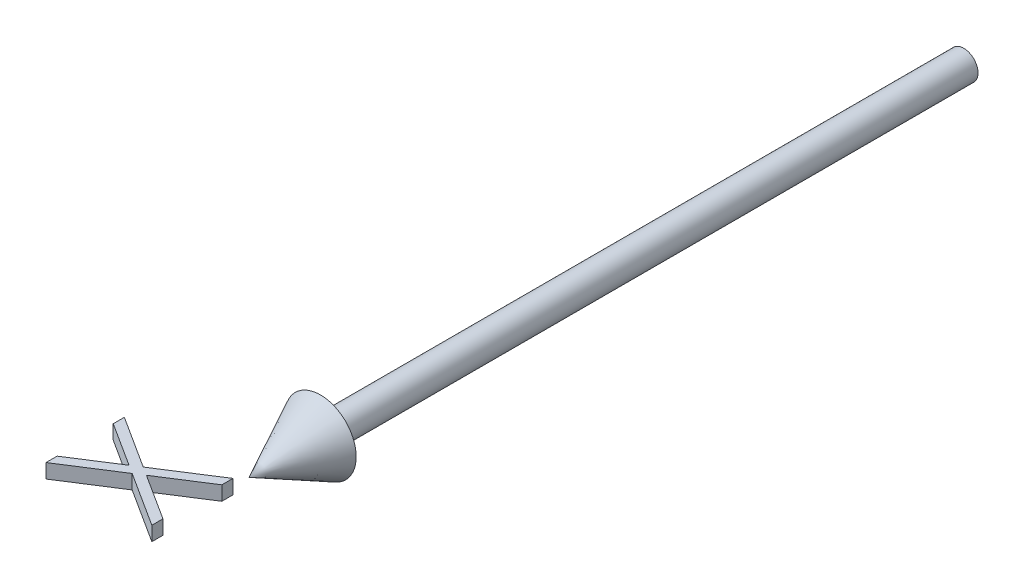
SolidWorks part; units mm, degrees
ref_plane "Front Plane" through (0, 0, 0) normal (0, 0, 1) x (1, 0, 0)
ref_plane "Top Plane" through (0, 0, 0) normal (0, 1, 0) x (1, 0, 0)
ref_plane "Right Plane" through (0, 0, 0) normal (1, 0, 0) x (0, 0, -1)
sketch "Sketch2" plane through (0, 0, 0) normal (0, 1, 0) x (1, 0, 0)
  line L0 (0, 41.95) -> (0, -114.4521) construction
  line L1 (-36.8894, 0) -> (41.4965, 0) construction
  line L2 (0, -100) -> (5, -90)
  line L3 (5, -90) -> (2, -90)
  line L4 (2, -90) -> (2, 0)
  line L5 (2, 0) -> (0, 0)
  line L6 (0, 0) -> (0, -100)
  dimension "D1" = 100
  dimension "D2" = 2
  dimension "D3" = 10
  dimension "D4" = 5
revolve "Revolve1" add sketch "Sketch2" angle 360 about L0
sketch "Sketch3" plane through (0, 0, 0) normal (0, 1, 0) x (1, 0, 0)
  line L0 (0, -101.5706) -> (0, -127.8138) construction
  line L1 (-18.6107, -118.3811) -> (18.3141, -118.3811) construction
  text T0 "X" font "Century Gothic" height 15
extrude "Boss-Extrude1" add sketch "Sketch3" against normal blind 1 and the other way blind 1 separate body
equation "\"frame_arrow_length\"=100"
equation "\"D1@Sketch2\"=\"frame_arrow_length\""
equation "\"frame_arrow_odA\"=4"
equation "\"D2@Sketch2\"=\"frame_arrow_odA\"/2"
equation "\"frame_arrow_head_od\"=5"
equation "\"D4@Sketch2\"=\"frame_arrow_head_od\""
equation "\"frame_arrow_head_length\"=10"
equation "\"D3@Sketch2\"=\"frame_arrow_head_length\""
equation "\"tvarobot_theta1\"=30"
equation "\"link0_ringA_odA\"= 40"
equation "\"link0_ringA_odB\"= 25"
equation "\"link0_ringA_id\"= 20"
equation "\"link0_ringA_thickness\"= (\"link0_ringA_odB\" - \"link0_ringA_id\")/2"
equation "\"link0_ringA_height\"= 3"
equation "\"link0_ringA_heightA\"= 1.5"
equation "\"link0_ringA_heightB\"=\"link0_ringA_height\"-\"link0_ringA_heightA\""
equation "\"link0_ringB_odA\"= 40"
equation "\"link0_ringB_odB\"= 29"
equation "\"link0_ringB_id\"= \"link0_shaftA_bearing_id\"+1"
equation "\"link0_ringB_thickness\"= (\"link0_ringB_odB\" - \"link0_ringB_id\")/2"
equation "\"link0_ringB_height\"= 3"
equation "\"link0_ringB_heightA\"= 1.5"
equation "\"link0_ringB_heightB\"=\"link0_ringB_height\"-\"link0_ringB_heightA\""
equation "\"link0_shaftA_bearing_od\"=27"
equation "\"link0_shaftA_bearing_id\"=20"
equation "\"link0_shaftA_thrust_bearing_od\"=35"
equation "\"link0_shaftA_thrust_bearing_id\"=20.04"
equation "\"link0_shaftA_retaining_ring_id\"=18.5"
equation "\"link0_shaftA_retaining_ring_groove_width\"=1.5"
equation "\"link0_shaftA_spline_length\"=8.0"
equation "\"link0_shaftA_spline_depth\"=1.0"
equation "\"link0_shaftA_spline_width\"=4.0"
equation "\"link0_shaftA_odA\"=\"link0_shaftA_bearing_id\""
equation "\"link0_shaftA_odB\"=35"
equation "\"link0_shaftA_odC\"=\"link0_shaftA_bearing_id\""
equation "\"link0_shaftA_odD\"=\"link0_shaftA_odC\"-2*\"link0_shaftA_spline_depth\""
equation "\"link0_shaftA_odE\"=\"link0_shaftA_bearing_id\""
equation "\"link0_shaftA_odF\"=\"link0_shaftA_odE\"-2*\"link0_shaftA_spline_depth\""
equation "\"link0_shaftA_idA\"=10"
equation "\"link0_shaftA_idB\"=6"
equation "\"link0_shaftA_length\"=39.5"
equation "\"link0_shaftA_lengthA\"=8.0"
equation "\"link0_shaftA_lengthB\"=12.0"
equation "\"link0_shaftA_lengthC\"=35.0"
equation "\"link0_shaftA_lengthD\"=39.0"
equation "\"link0_shaftA_lengthE\"=\"link0_shaftA_length\"-\"link0_shaftA_lengthD\""
equation "\"link0_shaftA_offsetX\"=11"
equation "\"link0_shaftA_offsetY\"=0"
equation "\"link0_shaftA_bolt_pattern_dia\"=14"
equation "\"link0_motor_center_dist\"=26"
equation "\"link0_46t_pulley_spline_length\"=8"
equation "\"link0_46t_pulley_spline_depth\"=\"link0_shaftA_spline_depth\"*1.025"
equation "\"link0_46t_pulley_spline_width\"=\"link0_shaftA_spline_width\"*1.05"
equation "\"link0_46t_pulley_idA\"=\"link0_shaftA_bearing_id\"*1.025"
equation "\"link0_46t_pulley_idB\"=\"link0_46t_pulley_idA\"-2*\"link0_46t_pulley_spline_depth\""
equation "\"link0_shaftB_spline_length\"=10"
equation "\"link0_shaftB_spline_depth\"=1.0"
equation "\"link0_shaftB_spline_width\"=1.25"
equation "\"link0_shaftB_length\"=7"
equation "\"link0_shaftB_lengthA\"=1.5"
equation "\"link0_shaftB_lengthB\"=2.75"
equation "\"link0_shaftB_odA\"=32"
equation "\"link0_shaftB_odB\"=22"
equation "\"link0_shaftB_odC\"=20"
equation "\"link0_shaftB_idA\"=10"
equation "\"link0_shaftB_bolt_diameter\"=19"
equation "\"link0_shaftB_bearing_od\"=27"
equation "\"link0_shaftB_bearing_id\"=20"
equation "\"link0_motor_length\"=46.5"
equation "\"link0_motor_width\"=28.5"
equation "\"link0_motor_height\"=34"
equation "\"link0_motor_offset\"=8"
equation "\"link0_shellA_thickness\"=2.5"
equation "\"link0_shellB_thickness\"=\"link0_shellA_thickness\""
equation "\"link0_plateA_shellA_height\"=48"
equation "\"link0_shellA_width\" =\"link0_plateA_width\""
equation "\"link0_shellA_height\" = \"link0_plateA_shellA_height\"-\"link0_plateA_height\""
equation "\"link0_shellA_length\" = \"link0_plateA_lengthB\" "
equation "\"link0_shellB_length\"=\"link0_shellA_length\""
equation "\"link0_shellA_radius\" = 0.375*25.4"
equation "\"link0_shellA_radiusA\"= \"link0_plateA_radiusA\""
equation "\"link0_shellA_radiusB\"= \"link0_plateA_radiusB\""
equation "\"link0_shellA_radiusC\"= 3"
equation "\"link0_postA_height\"=7"
equation "\"link0_postA_width\"=16"
equation "\"link0_postA_length\"=20"
equation "\"link0_postA_posX\"=22"
equation "\"link0_postA_posY\"=17.5"
equation "\"link0_postA_pocket_width\"=6.0"
equation "\"link0_postA_pocket_length\"=2.5"
equation "\"link0_postA_pocket_depth\"=9"
equation "\"link0_postA_pocket_posZ\"=10"
equation "\"link0_postB_height\"=7"
equation "\"link0_postB_width\"=16"
equation "\"link0_postB_length\"=20"
equation "\"link0_postB_posX\"=22"
equation "\"link0_postB_posY\"=17.5"
equation "\"link0_postB_id\"=3.0"
equation "\"link0_postB_pocket_width\"=6.0"
equation "\"link0_postB_pocket_length\"=2.5"
equation "\"link0_postB_pocket_depth\"=9"
equation "\"link0_postB_pocket_posZ\"=10"
equation "\"link0_postC_height\"=7"
equation "\"link0_postC_width\"=16"
equation "\"link0_postC_length\"=20"
equation "\"link0_postC_posX\"=22"
equation "\"link0_postC_posY\"=17.5"
equation "\"link0_postC_id\"=3.0"
equation "\"link0_postC_pocket_width\"=6.0"
equation "\"link0_postC_pocket_length\"=2.5"
equation "\"link0_postC_pocket_depth\"=9"
equation "\"link0_postC_pocket_posZ\"=10"
equation "\"link0_postD_height\"=7"
equation "\"link0_postD_width\"=16"
equation "\"link0_postD_length\"=20"
equation "\"link0_postD_posX\"=22"
equation "\"link0_postD_posY\"=17.5"
equation "\"link0_postD_id\"=3.0"
equation "\"link0_postD_pocket_width\"=6.0"
equation "\"link0_postD_pocket_length\"=3.0"
equation "\"link0_postD_pocket_depth\"=9"
equation "\"link0_postD_pocket_posZ\"=10"
equation "\"link0_postE_height\"=5"
equation "\"link0_postE_width\"=16"
equation "\"link0_postE_length\"=\"link0_plateE_lengthA\"-\"link0_lip_height\""
equation "\"link0_postE_posZ\"=22"
equation "\"link0_postE_posX\"=17.5"
equation "\"link0_postE_posY\"=22"
equation "\"link0_postE_id\"=3.0"
equation "\"link0_postE_cbore_id\"=6.5"
equation "\"link0_postE_hole_id\"=3"
equation "\"link0_postF_posZ\"=22"
equation "\"link0_postF_posX\"=17.5"
equation "\"link0_postF_posY\"=\"link0_plateB_lengthA\"+4"
equation "\"link0_postF_id\"=3.0"
equation "\"link0_postF_cbore_id\"=6.5"
equation "\"link0_postF_hole_id\"=3"
equation "\"link0_postG_posZ\"=22"
equation "\"link0_postG_posX\"=17.5"
equation "\"link0_postG_posY\"=\"link0_plateB_lengthA\"+12"
equation "\"link0_postG_id\"=3.0"
equation "\"link0_postG_cbore_id\"=6.5"
equation "\"link0_postG_hole_id\"=3"
equation "\"link0_postHIJ_posY\"=6"
equation "\"link0_postH_posX\"=28"
equation "\"link0_postH_posY\"=20"
equation "\"link0_postH_posZ\"=20"
equation "\"link0_postH_length\"=10"
equation "\"link0_postI_posX\"=28"
equation "\"link0_postI_posY\"=20"
equation "\"link0_postI_posZ\"=135"
equation "\"link0_postI_length\"=10"
equation "\"link0_postJ_posX\"=28"
equation "\"link0_postJ_posY\"=20"
equation "\"link0_postJ_posZ\"=175"
equation "\"link0_postJ_length\"=10"
equation "\"link0_postK_posX\"=28"
equation "\"link0_postK_posY\"=20"
equation "\"link0_postK_posZ\"=175"
equation "\"link0_postK_length\"=10"
equation "\"link0_postL_posX\"=28"
equation "\"link0_postL_posY\"=20"
equation "\"link0_postL_posZ\"=135"
equation "\"link0_postL_length\"=10"
equation "\"link0_postM_posX\"=28"
equation "\"link0_postM_posY\"=20"
equation "\"link0_postM_posZ\"=35"
equation "\"link0_postM_length\"=10"
equation "\"link0_plateA_lengthA\"=30"
equation "\"link0_plateA_lengthB\"=150"
equation "\"link0_plateA_lengthC\"=30"
equation "\"link0_plateA_length\"=\"link0_plateA_lengthA\"+\"link0_plateA_lengthB\"+\"link0_plateA_lengthC\""
equation "\"link0_plateA_width\"=  68"
equation "\"link0_plateA_height\"= \"link0_plateA_radiusA\""
equation "\"link0_plateA_thickness\"=\"link0_shellA_thickness\""
equation "\"link0_plateA_radius\"= 9.5"
equation "\"link0_plateA_radiusA\"= 18"
equation "\"link0_plateA_radiusB\"= 18"
equation "\"link0_plateA_radiusC\"= 3"
equation "\"link0_plateB_length\"= 40"
equation "\"link0_plateB_width\"= \"link0_plateA_width\"*1.005"
equation "\"link0_plateB_height\"= \"link0_plateA_shellA_height\"*1.005"
equation "\"link0_plateB_lengthA\"=\"link0_lip_height\"+\"link0_plateD_thickness\"+\"link0_motor_mount_thickness\""
equation "\"link0_plateB_lengthB\"=\"link0_plateB_height\"-\"link0_plateB_lengthA\""
equation "\"link0_plateB_radiusA\"= \"link0_plateA_radiusA\""
equation "\"link0_plateB_radiusB\"= \"link0_plateA_radiusB\""
equation "\"link0_plateB_radiusC\"= 3"
equation "\"link0_plateB_idA\"=\"link0_shaftA_odC\"+1"
equation "\"link0_plateB_idB\"=\"link0_shaftA_bearing_od\"-2"
equation "\"link0_plateB_idC\"=\"link0_shaftA_bearing_od\"*1.005"
equation "\"link0_plateB_idD\"=\"link0_shaftA_thrust_bearing_od\"+1 "
equation "\"link0_plateB_depthA\"=1.0"
equation "\"link0_plateB_depthB\"=2.0"
equation "\"link0_plateB_depthC\"=8"
equation "\"link0_plateB_depthD\"=\"link0_plateB_length\"-\"link0_lip_height\"-\"link0_plateD_thickness\" "
equation "\"link0_plateC_length\"=\"link0_plateB_length\""
equation "\"link0_plateC_width\"= \"link0_plateB_width\""
equation "\"link0_plateC_height\"= .1*25.4"
equation "\"link0_plateA_hole_od\" = 0.1*25.4"
equation "\"link0_plateA_hole_delx\" = 0.5*25.4"
equation "\"link0_plateA_hole_delz\" = 0.75*25.4"
equation "\"link0_plateA_hole_offx\" = 0.0*25.4"
equation "\"link0_plateA_hole_offz\" = \"link0_plateA_length\"/2"
equation "\"link0_plateB_hole_od\" = 0.1*25.4"
equation "\"link0_plateB_hole_delx\"= 0.75*25.4"
equation "\"link0_plateB_hole_delz\"= 0.75*25.4"
equation "\"link0_plateB_hole_offx\"= 0.0*25.4"
equation "\"link0_plateB_hole_offz\"= 0.0*25.4"
equation "\"link0_plateC_hole_od\"= 0.1*25.4"
equation "\"link0_plateC_hole_delx\"= 0.75*25.4"
equation "\"link0_plateC_hole_delz\"= 0.75*25.4"
equation "\"link0_plateC_hole_offx\"= 0.0*25.4"
equation "\"link0_plateC_hole_offz\"= 0.0*25.4"
equation "\"link0_plateD_height\"=\"link0_plateB_height\"-2*\"link0_shellA_thickness\""
equation "\"link0_plateD_width\"=\"link0_plateB_width\"-2*\"link0_shellA_thickness\""
equation "\"link0_plateD_thickness\"=10"
equation "\"link0_plateD_radiusA\"=\"link0_plateB_radiusA\"-\"link0_shellA_thickness\""
equation "\"link0_plateD_odA\"= .375*25.4"
equation "\"link0_plateD_odB\"= .375*25.4"
equation "\"link0_plateD_bearing_id\"=20"
equation "\"link0_plateD_bearing_od\"=27"
equation "\"link0_plateE_radiusA\"=\"link0_plateA_radiusA\""
equation "\"link0_plateE_radiusB\"=\"link0_plateA_radiusB\""
equation "\"link0_plateE_radiusC\"=8.0"
equation "\"link0_plateE_length\"=30"
equation "\"link0_plateE_lengthA\"=16"
equation "\"link0_plateE_height\"=\"link0_plateB_height\""
equation "\"link0_plateE_width\"=\"link0_plateB_width\""
equation "\"link0_plateE_odA\"=\"gantry_coupler_id\"*0.99"
equation "\"link0_plateE_idA\"=\"link0_plateE_odA\"-20.0"
equation "\"link0_plateE_spline_depth\"=\"link0_poleA_spline_depth\"*1.05"
equation "\"link0_plateE_spline_width\"=\"link0_poleA_spline_width\"*1.075"
equation "\"link0_plateE_spline_length\"=\"link0_poleA_spline_length\""
equation "\"link0_plateE_coupler_length\"=46"
equation "\"link0_lip_height\"=5.0"
equation "\"link0_lip_thickness\"=2.0"
equation "\"link0_motor_mount_thickness\"=8.0"
equation "\"link0_motor_mount_idA\"=22"
equation "\"link0_motor_mount_idB\"=\"link0_shaftB_bearing_od\"*1.005"
equation "\"link0_motor_mount_idC\"=\"link0_shaftB_bearing_od\"-2"
equation "\"link0_motor_mount_depthA\"=5.5"
equation "\"link0_motor_mount_height\"=\"link0_plateD_height\""
equation "\"link0_motor_mount_width\"=\"link0_plateD_width\""
equation "\"link0_motor_mountL_height\"=36"
equation "\"link0_motor_mountL_heightA\"=12"
equation "\"link0_motor_mountL_length\"=50"
equation "\"link0_motor_mountL_lengthA\"=36"
equation "\"gantry_coupler_od\"=25.4*2.0"
equation "\"gantry_coupler_id\"=1.645*25.4"
equation "\"gantry_coupler_offsetX\"=\"link0_plateE_width\"/2"
equation "\"link0_poleA_odA\"=20"
equation "\"link0_poleA_odB\"=36"
equation "\"link0_poleA_idA\"=\"link0_poleA_odA\"-2*\"link0_poleA_thickness\""
equation "\"link0_poleA_idB\"=(\"link0_plateE_idA\"/2+1.5*\"link0_lip_thickness\")*1.04"
equation "\"link0_poleA_thickness\"=3.5"
equation "\"link0_poleA_length\"=100"
equation "\"link0_poleA_lengthA\"=18.5"
equation "\"link0_poleA_lengthB\"=80"
equation "\"link0_poleA_gasket_thickness\"=1.5"
equation "\"link0_poleA_spline_depth\"=1.0"
equation "\"link0_poleA_spline_width\"=4.0"
equation "\"link0_poleA_spline_length\"=10.0"
equation "\"link1_plateB_length\"=30"
equation "\"link1_lip_height\"=\"link0_lip_height\""
equation "\"link0_tension_plateA_width\"=12"
equation "\"link0_tension_plateA_lengthA\"=10.5"
equation "\"link0_tension_plateB_width\"=\"link0_tension_plateA_width\""
equation "\"link0_tension_plateB_lengthA\"=\"link0_tension_plateA_lengthA\""
equation "\"link0_tension_wheelA_posZ\"=7"
equation "\"link0_tension_wheelA_posX\"=\"link0_plateD_height\"/2-\"link0_tension_plateA_lengthA\""
equation "\"link0_m2_clear_hole_id\"=2.35"
equation "\"link0_m2_insert_hole_id\"=2.5"
equation "\"link0_m2_tap_hole_id\"=1.75"
equation "\"link0_m2_nut_socket_width\"=4.25"
equation "\"link0_m2_nut_socket_depth\"=2.5"
equation "\"link0_m2_cbore_id\"=3.75"
equation "\"link0_m2_cbore_depth\"=7"
equation "\"link0_m2_5_clear_hole_id\"=2.75"
equation "\"link0_m2_5_insert_hole_id\"=2.75"
equation "\"link0_m2_5_tap_hole_id\"=2.25"
equation "\"link0_m2_5_nut_socket_width\"=5.25"
equation "\"link0_m2_5_nut_socket_depth\"=2.5"
equation "\"link0_m2_5_cbore_id\"=4.75"
equation "\"link0_m2_5_cbore_depth\"=2.5"
equation "\"link0_m2_5_insert_access_length\"=6.0"
equation "\"link0_m2_5_insert_access_width\"=3.0"
equation "\"link0_m3_clear_hole_id\"=3.25"
equation "\"link0_m3_insert_hole_id\"=3"
equation "\"link0_m3_tap_hole_id\"=2.75"
equation "\"link0_m3_nut_socket_width\"=5.75"
equation "\"link0_m3_nut_socket_depth\"=4.0"
equation "\"link0_m3_cbore_id\"=5.75"
equation "\"link0_m3_cbore_depth\"=3.5"
equation "\"link0_m3_insert_access_length\"=4.5"
equation "\"link0_m3_insert_access_width\"=3.5"
equation "\"link0_rpi_mount_height\"=6"
equation "\"link0_rpi_mount_width\"=49"
equation "\"link0_rpi_mount_length\"=58"
equation "\"link0_rpi_mount_post_od\"=6"
equation "\"link0_rpi_mount_posZ\"=72"
equation "\"link0_rpi_mount_posX\"=11.5"
equation "\"link0_mcu_mount_height\"=5"
equation "\"link0_mcu_mount_width\"=49"
equation "\"link0_mcu_mount_length\"=58"
equation "\"link0_mcu_mount_post_od\"=6"
equation "\"link0_mcu_mount_posZ\"=164"
equation "\"link0_mcu_mount_posX\"=4"
equation "\"link0_pwr_mount_height\"=4"
equation "\"link0_pwr_mount_width\"=15.75"
equation "\"link0_pwr_mount_length\"=75.75"
equation "\"link0_pwr_mount_post_od\"=6"
equation "\"link0_pwr_mount_posZ\"=75"
equation "\"link0_pwr_mount_posX\"=16"
equation "\"link0_pwr_board_height\"=6"
equation "\"link0_pwr_board_width\"=21"
equation "\"link0_pwr_board_length\"=80"
